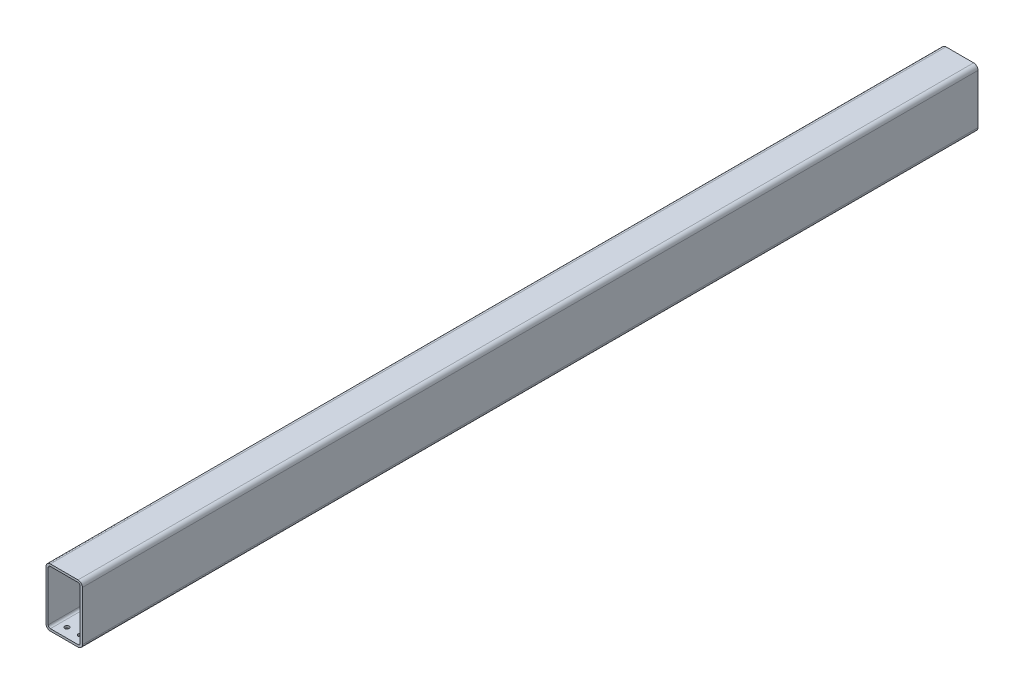
SolidWorks part; units mm, degrees
material "Plain Carbon Steel"
ref_plane "Front Plane" through (0, 0, 0) normal (0, 0, 1) x (1, 0, 0)
ref_plane "Top Plane" through (0, 0, 0) normal (0, 1, 0) x (1, 0, 0)
ref_plane "Right Plane" through (0, 0, 0) normal (1, 0, 0) x (0, 0, -1)
sketch "Sketch1" plane through (0, 0, 0) normal (0, 0, 1) x (1, 0, 0)
  line L0 (19, 40) -> (-19, 40)
  line L1 (19, -37) -> (-19, -37)
  line L2 (22, -34) -> (22, 34)
  line L3 (19, 37) -> (-19, 37)
  line L4 (-22, -34) -> (-22, 34)
  line L5 (22, -37) -> (-22, 37) construction
  line L6 (22, 37) -> (-22, -37) construction
  line L7 (-25, -34) -> (-25, 34)
  line L8 (19, -40) -> (-19, -40)
  line L9 (25, -34) -> (25, 34)
  line L10 (22, -37) -> (-22, -37) construction
  line L11 (22, -37) -> (22, 37) construction
  line L12 (-22, -37) -> (-22, 37) construction
  line L13 (22, 37) -> (-22, 37) construction
  line L14 (-25, -40) -> (-25, 40) construction
  line L15 (25, -40) -> (-25, -40) construction
  line L16 (25, -40) -> (25, 40) construction
  line L17 (25, 40) -> (-25, 40) construction
  arc A0 (19, -37) -> (22, -34) centre (19, -34) ccw
  arc A1 (-19, -37) -> (-22, -34) centre (-19, -34) cw
  arc A2 (-19, 37) -> (-22, 34) centre (-19, 34) ccw
  arc A3 (22, 34) -> (19, 37) centre (19, 34) ccw
  arc A4 (-25, -34) -> (-19, -40) centre (-19, -34) ccw
  arc A5 (19, -40) -> (25, -34) centre (19, -34) ccw
  arc A6 (19, 40) -> (25, 34) centre (19, 34) cw
  arc A7 (-19, 40) -> (-25, 34) centre (-19, 34) ccw
  point P0 (0, 0)
  dimension "D4" = 3
  dimension "D5" = 6
  dimension "D1" = 50
  dimension "D2" = 80
  dimension "D3" = 3
extrude "Boss-Extrude1" [suppressed] add sketch "Sketch1" along normal mid plane 100
sketch "Sketch2" [suppressed] plane through (-25, 0, 0) normal (-1, 0, 0) x (0, 0, 1)
  line L1 (20, -26.5) -> (-20, -26.5) construction
  line L2 (20, -26.5) -> (20, 26.5) construction
  line L3 (20, 26.5) -> (-20, 26.5) construction
  line L4 (-20, -26.5) -> (-20, 26.5) construction
  line L5 (20, -26.5) -> (-20, 26.5) construction
  line L6 (20, 26.5) -> (-20, -26.5) construction
  circle A0 centre (-20, 26.5) radius 3.3
  circle A1 centre (20, 26.5) radius 3.3
  circle A2 centre (20, -26.5) radius 3.3
  circle A3 centre (-20, -26.5) radius 3.3
  point P0 (0, 0)
  dimension "D3" = 6.6
  dimension "D1" = 40
  dimension "D2" = 53
extrude "Cut-Extrude1" [suppressed] cut sketch "Sketch2" against normal through all
sketch "Sketch3" [suppressed] plane through (0, -37, 0) normal (0, 1, 0) x (1, 0, 0)
  line L0 (0, 0) -> (3.6, 0) construction
  line L1 (25, -50) -> (25, 50) construction
  line L2 (14.85, 18) -> (-7.65, 18) construction
  line L3 (14.85, 18) -> (14.85, -18) construction
  line L4 (14.85, -18) -> (-7.65, -18) construction
  line L5 (-7.65, 18) -> (-7.65, -18) construction
  line L6 (14.85, 18) -> (-7.65, -18) construction
  line L7 (14.85, -18) -> (-7.65, 18) construction
  line L8 (-25, -50) -> (-25, 50) construction
  circle A0 centre (-7.65, 0) radius 2.5
  circle A1 centre (-7.65, 18) radius 2.5
  circle A2 centre (-7.65, -18) radius 2.5
  circle A3 centre (14.85, 18) radius 2.5
  circle A4 centre (14.85, -18) radius 2.5
  dimension "D1" = 5
  dimension "D2" = 36
  dimension "D4" = 10.15
  dimension "D3" = 17.35
extrude "Cut-Extrude2" [suppressed] cut sketch "Sketch3" against normal through all
sketch "Sketch4" [suppressed] plane through (0, 0, 0) normal (0, 0, 1) x (1, 0, 0)
  line L0 (25, -34) -> (25, 34) construction
  line L1 (19, -40) -> (-19, -40) construction
  line L2 (-25, -34) -> (-25, 34) construction
  line L3 (19, 40) -> (-19, 40) construction
  line L4 (22, -34) -> (22, 34) construction
  line L5 (19, -37) -> (-19, -37) construction
  line L6 (-22, -34) -> (-22, 34) construction
  line L7 (19, 37) -> (-19, 37) construction
  line L8 (25, -34) -> (25, 34)
  line L9 (19, -40) -> (-19, -40)
  line L10 (-25, -34) -> (-25, 34)
  line L11 (19, 40) -> (-19, 40)
  line L12 (22, -34) -> (22, 34)
  line L13 (19, -37) -> (-19, -37)
  line L14 (-22, -34) -> (-22, 34)
  line L15 (19, 37) -> (-19, 37)
  arc A0 (25, 34) -> (19, 40) centre (19, 34) ccw construction
  arc A1 (19, -40) -> (25, -34) centre (19, -34) ccw construction
  arc A2 (-25, -34) -> (-19, -40) centre (-19, -34) ccw construction
  arc A3 (-19, 40) -> (-25, 34) centre (-19, 34) ccw construction
  arc A4 (22, 34) -> (19, 37) centre (19, 34) ccw construction
  arc A5 (19, -37) -> (22, -34) centre (19, -34) ccw construction
  arc A6 (-22, -34) -> (-19, -37) centre (-19, -34) ccw construction
  arc A7 (-19, 37) -> (-22, 34) centre (-19, 34) ccw construction
  arc A8 (25, 34) -> (19, 40) centre (19, 34) ccw
  arc A9 (19, -40) -> (25, -34) centre (19, -34) ccw
  arc A10 (-25, -34) -> (-19, -40) centre (-19, -34) ccw
  arc A11 (-19, 40) -> (-25, 34) centre (-19, 34) ccw
  arc A12 (22, 34) -> (19, 37) centre (19, 34) ccw
  arc A13 (19, -37) -> (22, -34) centre (19, -34) ccw
  arc A14 (-22, -34) -> (-19, -37) centre (-19, -34) ccw
  arc A15 (-19, 37) -> (-22, 34) centre (-19, 34) ccw
extrude "Boss-Extrude2" [suppressed] add sketch "Sketch4" along normal mid plane 900
sketch "Sketch5" [suppressed] plane through (0, -40, 0) normal (0, -1, 0) x (1, 0, 0)
  line L0 (0, 275.729) -> (0, 77.6099) construction
  line L1 (7, -22) -> (-7, -22) construction
  line L2 (7, -22) -> (7, 22) construction
  line L3 (7, 22) -> (-7, 22) construction
  line L4 (-7, -22) -> (-7, 22) construction
  line L5 (7, -22) -> (-7, 22) construction
  line L6 (7, 22) -> (-7, -22) construction
  line L7 (-19, 450) -> (19, 450) construction
  line L8 (7, 388) -> (-7, 388) construction
  line L9 (7, 388) -> (7, 432) construction
  line L10 (7, 432) -> (-7, 432) construction
  line L11 (-7, 388) -> (-7, 432) construction
  line L12 (7, 388) -> (-7, 432) construction
  line L13 (7, 432) -> (-7, 388) construction
  line L14 (-122.9838, 0) -> (91.0788, 0) construction
  circle A0 centre (-7, 22) radius 3
  circle A1 centre (7, 22) radius 3
  circle A2 centre (-7, -22) radius 3
  circle A3 centre (7, -22) radius 3
  circle A4 centre (-7, 432) radius 3
  circle A5 centre (7, 432) radius 3
  circle A6 centre (-7, 388) radius 3
  circle A7 centre (7, 388) radius 3
  circle A8 centre (0, 410) radius 3
  circle A9 centre (7, -432) radius 3
  circle A10 centre (-7, -432) radius 3
  circle A11 centre (-7, -388) radius 3
  circle A12 centre (7, -388) radius 3
  circle A13 centre (0, -410) radius 3
  point P0 (0, 0)
  point P11 (0, 410)
  dimension "D1" = 6
  dimension "D2" = 14
  dimension "D3" = 44
  dimension "D4" = 18
extrude "Cut-Extrude3" [suppressed] cut sketch "Sketch5" against normal blind 20
sketch "Sketch6" [suppressed] plane through (0, 0, 0) normal (0, 0, 1) x (1, 0, 0)
  line L4 (22, -34) -> (22, 34)
  line L5 (-19, -37) -> (19, -37)
  line L6 (-22, 34) -> (-22, -34)
  line L7 (19, 37) -> (-19, 37)
  line L8 (22, -34) -> (22, 34)
  line L9 (-19, -37) -> (19, -37)
  line L10 (-22, 34) -> (-22, -34)
  line L11 (19, 37) -> (-19, 37)
  line L12 (19, 40) -> (-19, 40)
  line L13 (25, -34) -> (25, 34)
  line L14 (-19, -40) -> (19, -40)
  line L15 (-25, 34) -> (-25, -34)
  line L16 (19, 40) -> (-19, 40)
  line L17 (25, -34) -> (25, 34)
  line L18 (-19, -40) -> (19, -40)
  line L19 (-25, 34) -> (-25, -34)
  arc A4 (19, -37) -> (22, -34) centre (19, -34) ccw
  arc A5 (-22, -34) -> (-19, -37) centre (-19, -34) ccw
  arc A6 (-19, 37) -> (-22, 34) centre (-19, 34) ccw
  arc A7 (22, 34) -> (19, 37) centre (19, 34) ccw
  arc A8 (19, -37) -> (22, -34) centre (19, -34) ccw
  arc A9 (-22, -34) -> (-19, -37) centre (-19, -34) ccw
  arc A10 (-19, 37) -> (-22, 34) centre (-19, 34) ccw
  arc A11 (22, 34) -> (19, 37) centre (19, 34) ccw
  arc A12 (-19, 40) -> (-25, 34) centre (-19, 34) ccw
  arc A13 (25, 34) -> (19, 40) centre (19, 34) ccw
  arc A14 (19, -40) -> (25, -34) centre (19, -34) ccw
  arc A15 (-25, -34) -> (-19, -40) centre (-19, -34) ccw
  arc A16 (-19, 40) -> (-25, 34) centre (-19, 34) ccw
  arc A17 (25, 34) -> (19, 40) centre (19, 34) ccw
  arc A18 (19, -40) -> (25, -34) centre (19, -34) ccw
  arc A19 (-25, -34) -> (-19, -40) centre (-19, -34) ccw
  dimension "D1" = 0
  dimension "D2" = 0
extrude "Boss-Extrude3" [suppressed] add sketch "Sketch6" along normal mid plane 1200
sketch "Sketch7" [suppressed] plane through (-25, 0, 0) normal (-1, 0, 0) x (0, 0, 1)
  line L0 (0, 216.5319) -> (0, -154.0504) construction
  line L1 (-437.1299, 0) -> (-275.6774, 0) construction
  line L2 (-600, 34) -> (-600, -34) construction
  line L3 (-568, 22) -> (-582, 22) construction
  line L4 (-568, 22) -> (-568, -22) construction
  line L5 (-568, -22) -> (-582, -22) construction
  line L6 (-582, 22) -> (-582, -22) construction
  line L7 (-568, 22) -> (-582, -22) construction
  line L8 (-568, -22) -> (-582, 22) construction
  circle A0 centre (-582, 22) radius 3
  circle A1 centre (-568, 22) radius 3
  circle A2 centre (-568, -22) radius 3
  circle A3 centre (-582, -22) radius 3
  circle A4 centre (568, -22) radius 3
  circle A5 centre (582, -22) radius 3
  circle A6 centre (582, 22) radius 3
  circle A7 centre (568, 22) radius 3
  point P1 (-575, 0)
  dimension "D1" = 6
  dimension "D2" = 14
  dimension "D3" = 44
  dimension "D4" = 18
extrude "Cut-Extrude4" [suppressed] cut sketch "Sketch7" against normal through all and the other way through all
sketch "Sketch8" [suppressed] plane through (-25, 0, 0) normal (-1, 0, 0) x (0, 0, 1)
  line L0 (-582, 22) -> (-568, -22) construction
  line L1 (0, 84.5802) -> (0, -115.7286) construction
  circle A0 centre (-575, 0) radius 3
  circle A1 centre (-568, 22) radius 3 construction
  circle A2 centre (575, 0) radius 3
extrude "Cut-Extrude5" [suppressed] cut sketch "Sketch8" against normal blind 20
sketch "Sketch9" plane through (0, 0, 0) normal (0, 0, 1) x (1, 0, 0)
  line L4 (22, -34) -> (22, 34)
  line L5 (-19, -37) -> (19, -37)
  line L6 (-22, 34) -> (-22, -34)
  line L7 (19, 37) -> (-19, 37)
  line L8 (22, -34) -> (22, 34)
  line L9 (-19, -37) -> (19, -37)
  line L10 (-22, 34) -> (-22, -34)
  line L11 (19, 37) -> (-19, 37)
  line L12 (19, 40) -> (-19, 40)
  line L13 (25, -34) -> (25, 34)
  line L14 (-19, -40) -> (19, -40)
  line L15 (-25, 34) -> (-25, -34)
  line L16 (19, 40) -> (-19, 40)
  line L17 (25, -34) -> (25, 34)
  line L18 (-19, -40) -> (19, -40)
  line L19 (-25, 34) -> (-25, -34)
  arc A4 (19, -37) -> (22, -34) centre (19, -34) ccw
  arc A5 (-22, -34) -> (-19, -37) centre (-19, -34) ccw
  arc A6 (-19, 37) -> (-22, 34) centre (-19, 34) ccw
  arc A7 (22, 34) -> (19, 37) centre (19, 34) ccw
  arc A8 (19, -37) -> (22, -34) centre (19, -34) ccw
  arc A9 (-22, -34) -> (-19, -37) centre (-19, -34) ccw
  arc A10 (-19, 37) -> (-22, 34) centre (-19, 34) ccw
  arc A11 (22, 34) -> (19, 37) centre (19, 34) ccw
  arc A12 (-19, 40) -> (-25, 34) centre (-19, 34) ccw
  arc A13 (25, 34) -> (19, 40) centre (19, 34) ccw
  arc A14 (19, -40) -> (25, -34) centre (19, -34) ccw
  arc A15 (-25, -34) -> (-19, -40) centre (-19, -34) ccw
  arc A16 (-19, 40) -> (-25, 34) centre (-19, 34) ccw
  arc A17 (25, 34) -> (19, 40) centre (19, 34) ccw
  arc A18 (19, -40) -> (25, -34) centre (19, -34) ccw
  arc A19 (-25, -34) -> (-19, -40) centre (-19, -34) ccw
  dimension "D1" = 0
  dimension "D2" = 0
extrude "Boss-Extrude4" add sketch "Sketch9" along normal mid plane 1230
sketch "Sketch10" plane through (0, -40, 0) normal (0, -1, 0) x (1, 0, 0)
  line L0 (-413.5216, 0) -> (284.1515, 0) construction
  line L1 (0, 0) -> (0, 615) construction
  line L2 (-19, 615) -> (19, 615) construction
  line L4 (9.225, 548) -> (-9.225, 548) construction
  line L5 (9.225, 548) -> (9.225, 602) construction
  line L6 (9.225, 602) -> (-9.225, 602) construction
  line L7 (-9.225, 548) -> (-9.225, 602) construction
  line L8 (9.225, 548) -> (-9.225, 602) construction
  line L9 (9.225, 602) -> (-9.225, 548) construction
  circle A0 centre (-9.225, 602) radius 3
  circle A1 centre (9.225, 602) radius 3
  circle A2 centre (9.225, 548) radius 3
  circle A3 centre (-9.225, 548) radius 3
  circle A4 centre (9.225, -548) radius 3
  circle A5 centre (-9.225, -548) radius 3
  circle A6 centre (9.225, -602) radius 3
  circle A7 centre (-9.225, -602) radius 3
  point P7 (0, 575)
  dimension "D1" = 6
  dimension "D2" = 18.45
  dimension "D3" = 54
  dimension "D4" = 13
extrude "Cut-Extrude6" cut sketch "Sketch10" against normal blind 20
equation "\"length\"= 100"
equation "\"D1@Boss-Extrude1\"=\"length\""
equation "\"D3@Sketch2\"=\"M6_clearence\""
equation "\"D1@Sketch3\"=\"M6_tap\""
equation "\"M5_tap\"=4.2mm"
equation "\"M5_clearence\"=5.5mm"
equation "\"M6_tap\"=5mm"
equation "\"M6_clearence\"=6.6mm"
equation "\"work_area_width\"=1100mm"
equation "\"work_area_depth\"=900mm"
equation "\"D1@Boss-Extrude2\"=\"work_area_depth\""
equation "\"D1@Boss-Extrude3\"=\"work_area_width\" + (50*2)"
equation "\"D1@Boss-Extrude4\"=\"work_area_width\" + 130mm"
